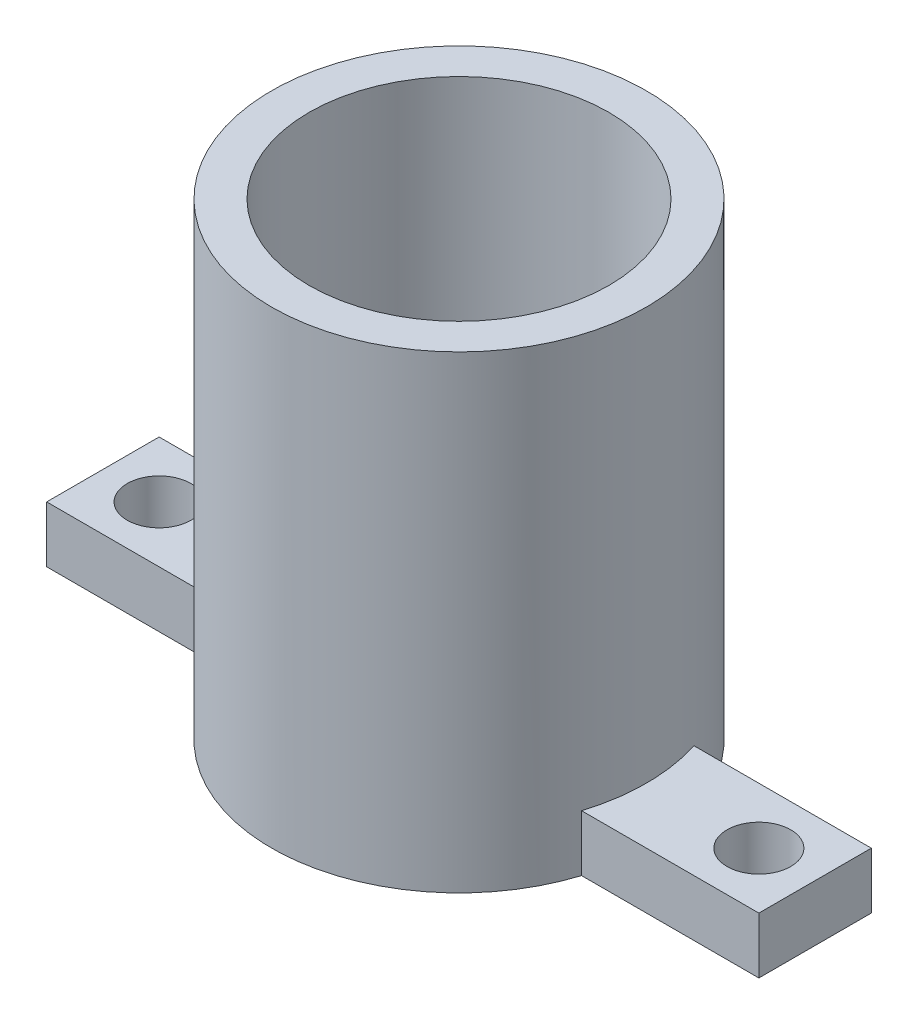
SolidWorks part; units mm, degrees
ref_plane "Front Plane" through (0, 0, 0) normal (0, 0, 1) x (1, 0, 0)
ref_plane "Top Plane" through (0, 0, 0) normal (0, 1, 0) x (1, 0, 0)
ref_plane "Right Plane" through (0, 0, 0) normal (1, 0, 0) x (0, 0, -1)
sketch "Sketch1" plane through (0, 0, 0) normal (0, 1, 0) x (1, 0, 0)
  line L0 (28.5394, 0) -> (38, 0)
  line L1 (0, 0) -> (9.4606, 0)
  line L2 (0, 0) -> (0, 6)
  line L3 (0, 6) -> (9.4606, 6)
  line L4 (38, 0) -> (38, 6)
  line L5 (28.5394, 6) -> (38, 6)
  circle A0 centre (19, 3) radius 8
  circle A1 centre (19, 3) radius 10
  point P8 (38, 3)
  point P12 (0, 0)
  point P13 (0, 0)
  dimension "D3" = 16
  dimension "D4" = 20
  dimension "D1" = 38
  dimension "D2" = 6
extrude "Boss-Extrude1" add sketch "Sketch1" along normal blind 3 contours A1 L0 L4 L5 | A1 L3 L2 L1 region at (33.4229, 0, -3) region at (4.5771, 0, -3)
extrude "Boss-Extrude2" add sketch "Sketch1<3>" along normal blind 25 contours A1 A0 region at (19, 0, 6.7172)
sketch "Sketch1<3>" plane through (0, 0, 0) normal (0, 1, 0) x (1, 0, 0) same geometry as "Sketch1"
sketch "Sketch4" plane through (0, 3, 0) normal (0, 1, 0) x (1, 0, 0)
  line L1 (0, 0) -> (0, 6) construction
  line L3 (0, 6) -> (9.4606, 6) construction
  point P0 (3, 3)
  point P2 (35, 3)
  point P4 (0, 0)
  dimension "D1" = 32
  dimension "D2" = 3
  dimension "D3" = 3
hole_wizard "M3 Clearance Hole1" positions "Sketch4" profile "Sketch3" hole size "M3" standard "ANSI Metric" end condition through all
sketch "Sketch3" plane through (3, 3, -3) normal (1, 0, 0) x (0, 0, 1)
  line L0 (0, 0) -> (0, 3)
  line L1 (0, 3) -> (1.7, 3)
  line L2 (1.7, 3) -> (1.7, 0)
  line L5 (1.7, 0) -> (0, 0)
  line L11 (0, -6.35) -> (0, 107.95) construction
  dimension "Thru Hole Dia." = 3.4
  dimension "Thru Hole Depth" = 3
